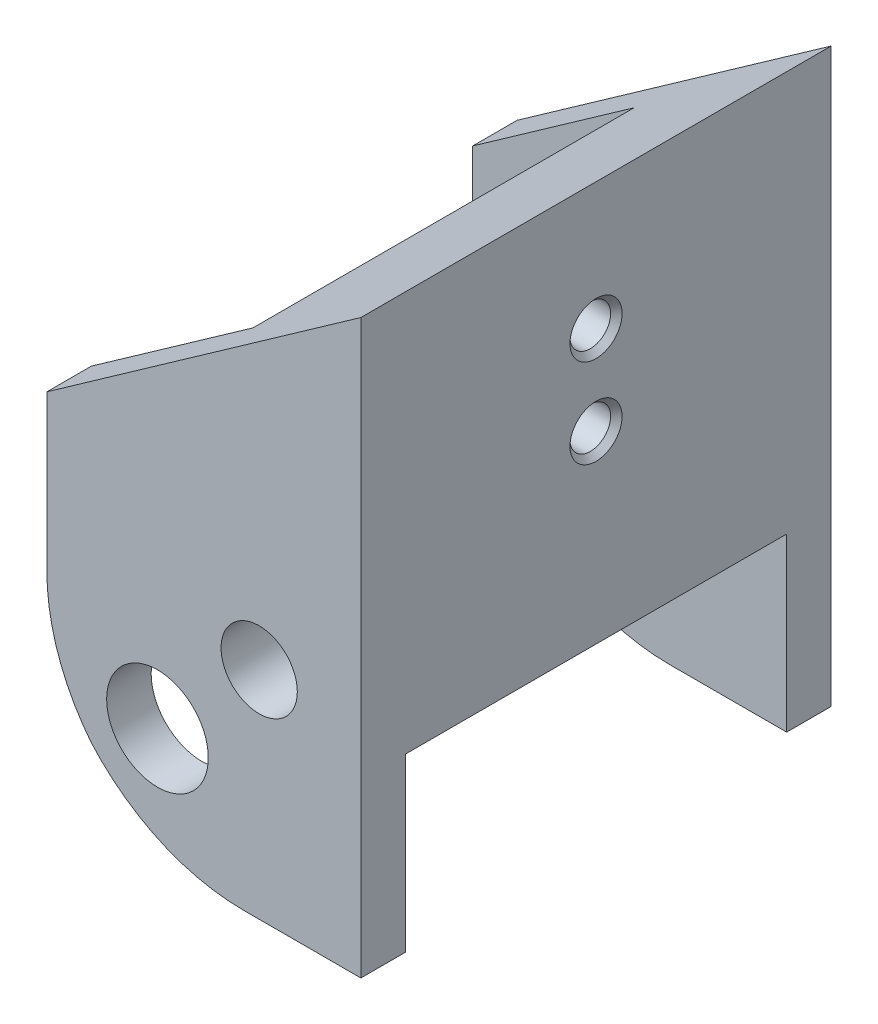
SolidWorks part; units mm, degrees
ref_plane "Front Plane" through (0, 0, 0) normal (0, 0, 1) x (1, 0, 0)
ref_plane "Top Plane" through (0, 0, 0) normal (0, 1, 0) x (1, 0, 0)
ref_plane "Right Plane" through (0, 0, 0) normal (1, 0, 0) x (0, 0, -1)
sketch "Sketch1" plane through (0, 0, 0) normal (0, 0, 1) x (1, 0, 0)
  line L0 (-7.2764, -10.5186) -> (2.2236, -16.0034)
  line L1 (2.2236, -16.0034) -> (6.2236, -16.0034)
  line L2 (-7.2764, -10.5186) -> (-7.2764, -0.5186)
  line L4 (6.2236, -16.0034) -> (6.2236, 8.9966)
  line L5 (-7.2764, -10.5186) -> (6.2236, 8.9966) construction
  line L6 (-1.4071, 3.6183) -> (6.2236, -16.0034) construction
  line L7 (-7.2764, -0.5186) -> (6.2236, 8.9966)
  point P0 (0, 0)
  dimension "D1" = 13.5
  dimension "D2" = 25
  dimension "D3" = 4
  dimension "D4" = 30
  dimension "D5" = 10
extrude "Boss-Extrude1" add sketch "Sketch1" along normal blind 18.5
sketch "Sketch2" plane through (0, 0, 0) normal (0, 0, -1) x (-1, 0, 0)
  line L0 (7.2764, -0.5186) -> (7.2764, -10.5186) construction
  line L1 (-6.2236, -16.0034) -> (-6.2236, 8.9966) construction
  line L3 (-2.2236, -16.0034) -> (-6.2236, -16.0034) construction
  circle A0 centre (1.7764, -9.0034) radius 2
  circle A1 centre (-2.2236, -5.0034) radius 1.5
  dimension "D1" = 4
  dimension "D2" = 3
  dimension "D3" = 5.5
  dimension "D4" = 4
  dimension "D5" = 7
  dimension "D6" = 11
extrude "Cut-Extrude1" cut sketch "Sketch2" against normal through all contours A0 region at (-1.7764, -9.0034, 0)
extrude "Cut-Extrude2" cut sketch "Sketch2<3>" against normal blind 7 contours A1 region at (2.2236, -5.0034, 0)
sketch "Sketch2<3>" plane through (0, 0, 0) normal (0, 0, -1) x (-1, 0, 0) same geometry as "Sketch2"
sketch "Sketch5" plane through (0, 0, 0) normal (0, 0, -1) x (-1, 0, 0)
  line L0 (-6.2236, -13.5034) -> (2.1066, -13.5034)
  line L1 (-6.2236, -16.0034) -> (-6.2236, 8.9966) construction
  line L2 (7.2764, -10.5186) -> (-2.2236, -16.0034) construction
  line L3 (2.1066, -13.5034) -> (-2.2236, -16.0034)
  line L4 (-2.2236, -16.0034) -> (-6.2236, -16.0034)
  line L5 (-6.2236, -16.0034) -> (-6.2236, -13.5034)
  dimension "D1" = 2.5
extrude "Cut-Extrude3" cut sketch "Sketch5" against normal through all
sketch "Sketch6" plane through (0, 0, 0) normal (0, 0, -1) x (-1, 0, 0)
  line L0 (2.1066, -13.5034) -> (7.2764, -7.3422)
  line L1 (7.2764, -0.5186) -> (7.2764, -10.5186) construction
  line L2 (7.2764, -7.3422) -> (7.2764, -10.5186)
  line L3 (7.2764, -10.5186) -> (2.1066, -13.5034)
  dimension "D1" = 20
extrude "Cut-Extrude4" cut sketch "Sketch6" against normal through all
sketch "Sketch7" plane through (6.2236, 0, 0) normal (1, 0, 0) x (0, 0, -1)
  line L0 (-9.25, 8.9966) -> (-9.25, -14.2492) construction
  line L1 (-18.5, 8.9966) -> (0, 8.9966) construction
  line L11 (-18.5, -13.5034) -> (0, -13.5034) construction
  line L12 (-16.75, -13.5034) -> (-1.75, -13.5034)
  line L13 (-16.75, -13.5034) -> (-16.75, -6.7534)
  line L14 (-16.75, -6.7534) -> (-1.75, -6.7534)
  line L15 (-1.75, -13.5034) -> (-1.75, -6.7534)
  line M7 (-18.5, -13.5034) -> (0, -13.5034)
  dimension "D1" = 7.5
  dimension "D2" = 6.75
  dimension "D3" = 7.5
extrude "Cut-Extrude5" cut sketch "Sketch7" against normal through all contours L15 L14 L13 M7 | M7 region at (6.2236, -10.1284, 9.25)
sketch "Sketch11" plane through (0, -6.7534, 0) normal (0, -1, 0) x (1, 0, 0)
  line L0 (-7.2764, 16.75) -> (-7.2764, 1.75) construction
  line L1 (-7.2764, 16.75) -> (0.2236, 16.75)
  line L2 (-7.2764, 16.75) -> (-7.2764, 1.75)
  line L3 (-7.2764, 1.75) -> (0.2236, 1.75)
  line L4 (0.2236, 16.75) -> (0.2236, 1.75)
  line L5 (-7.2764, 16.75) -> (6.2236, 16.75) construction
  line L6 (-7.2764, 1.75) -> (6.2236, 1.75) construction
  dimension "D1" = 7.5
extrude "Cut-Extrude6" cut sketch "Sketch11" against normal through all
hole_wizard "M2x0.4 Tapped Hole1" positions "Sketch9" profile "Sketch10" tap size "M2x0.4" standard "ANSI Metric"
sketch "Sketch9" plane through (6.2236, 0, 0) normal (1, 0, 0) x (0, 0, -1)
  line L2 (0, -13.5034) -> (0, 8.9966) construction
  line L3 (-18.5, -13.5034) -> (-18.5, 8.9966) construction
  line L4 (-18.5, 8.9966) -> (0, 8.9966) construction
  point P0 (-9.25, 3.9966)
  point P2 (-9.25, 0.4966)
  dimension "D1" = 9.25
  dimension "D2" = 3.5
  dimension "D3" = 9.25
  dimension "D4" = 5
cosmetic thread "Hole Thread1" parameters "D1"=6.07, "D2"=2
cosmetic thread "Hole Thread2" parameters "D1"=6.07, "D2"=2
sketch "Sketch10" plane through (6.2236, 3.9966, 9.25) normal (0, 1, 0) x (0, 0, -1)
  line L0 (0, 0) -> (0, 4.4807)
  line L1 (0, 4.4807) -> (0.8, 4)
  line L2 (0.8, 4) -> (0.8, 0.225)
  line L3 (0.8, 0.225) -> (1.025, 0)
  line L5 (1.025, 0) -> (0, 0)
  line L6 (-0.8, 0.225) -> (-1.025, 0) construction
  line L10 (0, 4.4807) -> (-0.8, 4) construction
  line L11 (0, -6.35) -> (0, 107.95) construction
  dimension "Tap Drill Dia." = 1.6
  dimension "Tap Drill Depth" = 4
  dimension "Near C'Sink Dia." = 2.05
  dimension "Near C'Sink Angle" = 90
  dimension "Drill Angle" = 118
sketch "Sketch12" plane through (0, 0, 18.5) normal (0, 0, 1) x (1, 0, 0)
  line L0 (6.2236, -13.5034) -> (6.2236, 8.9966) construction
  line L1 (-2.1066, -13.5034) -> (6.2236, -13.5034) construction
  circle A0 centre (2.2236, -5.0034) radius 1.5
  dimension "D1" = 3
  dimension "D2" = 4
  dimension "D3" = 8.5
extrude "Cut-Extrude7" cut sketch "Sketch12" against normal blind 7
sketch "Sketch13" plane through (0, 0, 18.5) normal (0, 0, 1) x (1, 0, 0)
  line L0 (-6.1289, -8.7098) -> (-6.1289, 0.2902)
  line L1 (-7.2764, -7.3422) -> (-2.1066, -13.5034) construction
  line L2 (6.2236, 8.9966) -> (-7.2764, -0.5186) construction
  line L3 (-6.1289, 0.2902) -> (-7.2764, -0.5186)
  line L4 (-7.2764, -0.5186) -> (-7.2764, -7.3422)
  line L5 (-7.2764, -7.3422) -> (-6.1289, -8.7098)
  dimension "D1" = 9
extrude "Cut-Extrude8" cut sketch "Sketch13" against normal through all
fillet "Fillet1" radius 8 4 edges at (-6.1289, -8.7098, 0.875) (-2.1066, -13.5034, 0.875) (-6.1289, -8.7098, 17.625) (-2.1066, -13.5034, 17.625)
